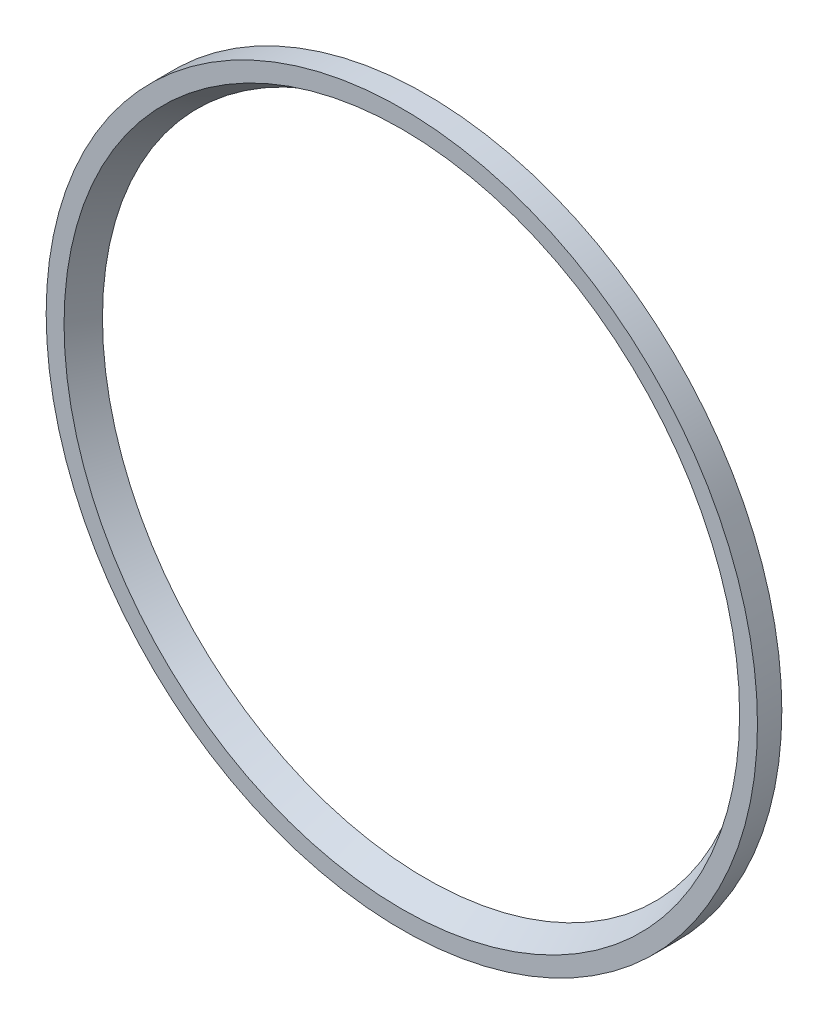
SolidWorks part; units mm, degrees
ref_plane "Front Plane" through (0, 0, 0) normal (0, 0, 1) x (1, 0, 0)
ref_plane "Top Plane" through (0, 0, 0) normal (0, 1, 0) x (1, 0, 0)
ref_plane "Right Plane" through (0, 0, 0) normal (1, 0, 0) x (0, 0, -1)
sketch "Sketch1" plane through (0, 0, 0) normal (0, 0, 1) x (1, 0, 0)
  circle A0 centre (0, 0) radius 18.542
  circle A1 centre (0, 0) radius 16.51
  dimension "D1" = 2.032
  dimension "D2" = 33.02
extrude "Boss-Extrude1" add sketch "Sketch1" along normal blind 1.27
chamfer "Chamfer1" distance 1.905 angle 30 1 edges at (16.51, 0, 1.27) first distance on face at (16.51, 0, 1.27)
